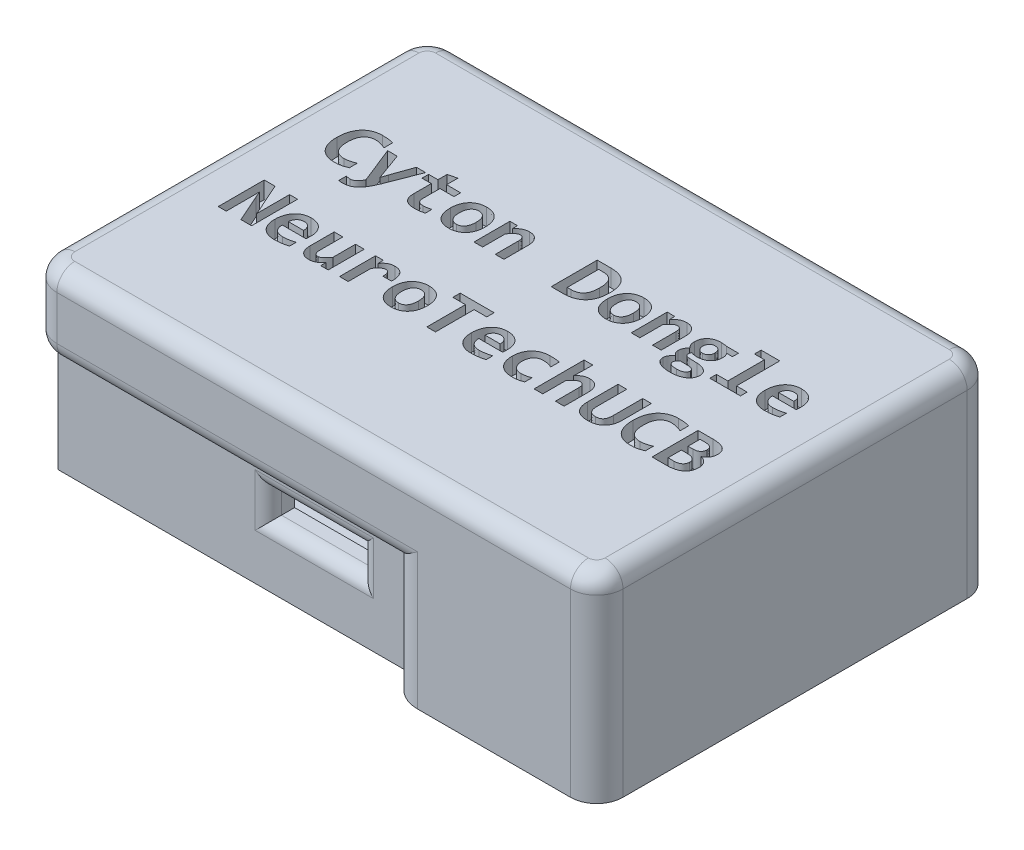
SolidWorks part; units mm, degrees
ref_plane "Alzado" through (0, 0, 0) normal (0, 0, 1) x (1, 0, 0)
ref_plane "Planta" through (0, 0, 0) normal (0, 1, 0) x (1, 0, 0)
ref_plane "Vista lateral" through (0, 0, 0) normal (1, 0, 0) x (0, 0, -1)
sketch "Croquis1" plane through (0, 0, 0) normal (0, 1, 0) x (1, 0, 0)
  line L1 (18.55, 11.05) -> (-18.55, 11.05)
  line L2 (18.55, 11.05) -> (18.55, -11.05)
  line L3 (18.55, -11.05) -> (-18.55, -11.05)
  line L4 (-18.55, 11.05) -> (-18.55, -11.05)
  line L5 (18.55, 11.05) -> (-18.55, -11.05) construction
  line L6 (18.55, -11.05) -> (-18.55, 11.05) construction
  point P0 (0, 0)
  dimension "D1" = 37.1
  dimension "D2" = 22.1
extrude "Saliente-Extruir1" add sketch "Croquis1" along normal blind 11
shell "Vaciado1" thickness 2 removed face at (0, 11, 0) outward yes
sketch "Croquis2" plane through (-20.55, 0, 0) normal (-1, 0, 0) x (0, 0, 1)
  line L0 (-13.05, 4.5) -> (13.05, 4.5) construction
  line L1 (-13.05, 11) -> (-13.05, -2) construction
  line L2 (13.05, 11) -> (13.05, -2) construction
  line L3 (0, 11) -> (0, -2) construction
  line L4 (-13.05, 11) -> (13.05, 11) construction
  line L5 (-13.05, -2) -> (13.05, -2) construction
  line L7 (-7, 11) -> (7, 11)
  line L8 (-7, 11) -> (-7, 0)
  line L9 (-7, 0) -> (7, 0)
  line L10 (7, 11) -> (7, 0)
  line L11 (-7, 11) -> (7, 0) construction
  line L12 (-7, 0) -> (7, 11) construction
  line L14 (-11.05, 0) -> (11.05, 0) construction
  point P12 (0, 5.5)
  dimension "D1" = 14
extrude "Cortar-Extruir1" cut sketch "Croquis2" against normal up to surface (2 mm away) up to face at (-18.55, 5.5, 0)
sketch "Croquis3" plane through (0, 0, 13.05) normal (0, 0, 1) x (1, 0, 0)
  line L0 (14.355, 0) -> (-14.355, 0) construction
  line L1 (2.45, 4.5) -> (-4.55, 4.5)
  line L2 (2.45, 4.5) -> (2.45, 2.5)
  line L3 (2.45, 2.5) -> (-4.55, 2.5)
  line L4 (-4.55, 4.5) -> (-4.55, 2.5)
  line L5 (2.45, 4.5) -> (-4.55, 2.5) construction
  line L6 (2.45, 2.5) -> (-4.55, 4.5) construction
  line L7 (-18.55, 11) -> (-18.55, 0) construction
  point P0 (-1.05, 3.5)
  dimension "D1" = 2.5
  dimension "D2" = 2
  dimension "D3" = 7
  dimension "D4" = 14
extrude "Cortar-Extruir2" cut sketch "Croquis3" against normal up to surface (2 mm away) up to face at (0, 5.5, 11.05)
sketch "Croquis4" plane through (0, 0, 0) normal (0, 1, 0) x (1, 0, 0)
  line L0 (-20.55, -13.15) -> (-20.55, -15.15)
  line L2 (-20.55, -15.15) -> (22.55, -15.15)
  line L4 (22.55, -15.15) -> (22.55, 15.05)
  line L5 (22.55, 15.05) -> (-20.55, 15.05)
  line L6 (-20.55, 15.05) -> (-20.55, 13.15)
  line L7 (20.55, 13.05) -> (-20.55, 13.05) construction
  line L8 (20.55, -13.05) -> (20.55, 13.05) construction
  line L12 (-20.55, 13.15) -> (20.65, 13.15)
  line L13 (20.65, 13.15) -> (20.65, -13.15)
  line L14 (-20.55, -13.05) -> (20.55, -13.05) construction
  line L15 (-20.55, -13.15) -> (20.65, -13.15)
  dimension "D1" = 0.1
  dimension "D2" = 2
  dimension "D3" = 2
  dimension "D6" = 0.1
  dimension "D7" = 0.1
  dimension "D8" = 2
extrude "Saliente-Extruir2" add sketch "Croquis4" along normal up to surface and the other way up to surface
sketch "Croquis5" plane through (0, 0, 15.15) normal (0, 0, 1) x (1, 0, 0)
  line L0 (-20.55, 7) -> (6.45, 7)
  line L1 (-20.55, 11) -> (-20.55, -2) construction
  line L2 (6.45, 7) -> (6.45, -2)
  line L5 (-20.55, -2) -> (22.55, -2) construction
  dimension "D1" = 27
  dimension "D3" = 9
extrude "Cortar-Extruir3" cut sketch "Croquis5" against normal blind 2 and the other way through all
mirror "Simetría1" about plane through (0, 0, 0) normal (0, 0, 1) of "Cortar-Extruir3"
sketch "Croquis6" plane through (0, 11, 0) normal (0, 1, 0) x (1, 0, 0)
  line L0 (22.55, 15.05) -> (22.55, -15.15)
  line L1 (22.55, 15.05) -> (-20.55, 15.05)
  line L2 (22.55, -15.15) -> (-20.55, -15.15)
  line L3 (-20.55, 15.05) -> (-20.55, -15.15)
  line L4 (-20.55, -7) -> (-20.55, -13.05) construction
extrude "Saliente-Extruir3" add sketch "Croquis6" along normal blind 2 from offset 0.1 separate body
sketch "Croquis7" plane through (0, 11.1, 0) normal (0, -1, 0) x (1, 0, 0)
  line L0 (-20.55, -6.9) -> (-18.55, -6.9)
  line L1 (-18.55, -6.9) -> (-18.55, 6.9)
  line L2 (-18.55, 6.9) -> (-20.55, 6.9)
  line L3 (-20.55, 6.9) -> (-20.55, -6.9)
  line L6 (-20.55, -15.05) -> (-20.55, 15.15) construction
  line L7 (-18.55, -7) -> (-20.55, -7) construction
  line L8 (-18.55, 7) -> (-20.55, 7) construction
  dimension "D1" = 0.1
  dimension "D2" = 0.1
  dimension "D3" = 2
extrude "Saliente-Extruir4" add sketch "Croquis7" along normal blind 7
sketch "Croquis9" plane through (0, 11, 0) normal (0, 1, 0) x (1, 0, 0)
  line L0 (-20.55, 13.15) -> (-20.55, 15.05)
  line L1 (-20.55, 15.05) -> (22.55, 15.05)
  line L2 (22.55, 15.05) -> (22.55, -15.15)
  line L3 (22.55, -15.15) -> (-20.55, -15.15)
  line L4 (-20.55, -15.15) -> (-20.55, -13.15)
  line L5 (-20.55, 15.05) -> (-20.55, -15.15) construction
  line L6 (-20.55, 13.15) -> (20.55, 13.05)
  line L7 (20.55, 13.05) -> (20.55, -13.05)
  line L8 (20.55, -13.05) -> (-20.55, -13.15)
extrude "Saliente-Extruir5" add sketch "Croquis9" along normal up to surface (0.1 mm away) up to face at (-9.275, 11.1, 0.025)
fillet "Redondeo1" radius 2.5 2 edges at (6.45, 2.5, 15.15) (6.45, 2.5, -15.05)
fillet "Redondeo2" radius 2 4 edges at (-20.55, 10.05, 15.15) (22.55, 5.55, 15.15) (22.55, 5.55, -15.05) (-20.55, 10.05, -15.05)
fillet "Redondeo4" radius 1 4 edges at (-4.55, 3.5, 13.05) (-1.05, 4.5, 13.05) (2.45, 3.5, 13.05) (-1.05, 2.5, 13.05)
fillet "Redondeo5" radius 0.8 1 edges at (-20.55, 0, 0)
fillet "Redondeo6" radius 0.8 2 edges at (-18.55, 4.1, 0) (-20.55, 4.1, 0)
fillet "Redondeo7" radius 1.3666 8 edges at (21.9642, 13.1, -14.4642) (22.55, 13.1, 0.05) (21.9642, 13.1, 14.5642) (1, 13.1, 15.15) (-19.9642, 13.1, 14.5642) (-20.55, 13.1, 0.05) (-19.9642, 13.1, -14.4642) (1, 13.1, -15.05)
fillet "Redondeo8" radius 1.3666 4 edges at (-19.9284, 7, -14.4991) (-19.9642, 7, 14.5642) (-4.8365, 7, -15.05) (-4.8253, 7, 15.15)
sketch "Croquis10" plane through (0, 13.1, 0) normal (0, 1, 0) x (1, 0, 0)
  line L0 (-19.1834, 2.6834) -> (21.1834, 2.6834) construction
  line L3 (-19.1834, 13.05) -> (-19.1834, -13.15) construction
  line L4 (20.55, 13.6834) -> (-18.55, 13.6834) construction
  line L5 (21.1834, -13.15) -> (21.1834, 13.05) construction
  text T0 "Cyton Dongle\r\nNeuroTechUCB" font "Consolas" height 3.5
  dimension "D1" = 11
extrude "Cortar-Extruir4" cut sketch "Croquis10" against normal blind 1.3
other "Guardar sólidos1"
